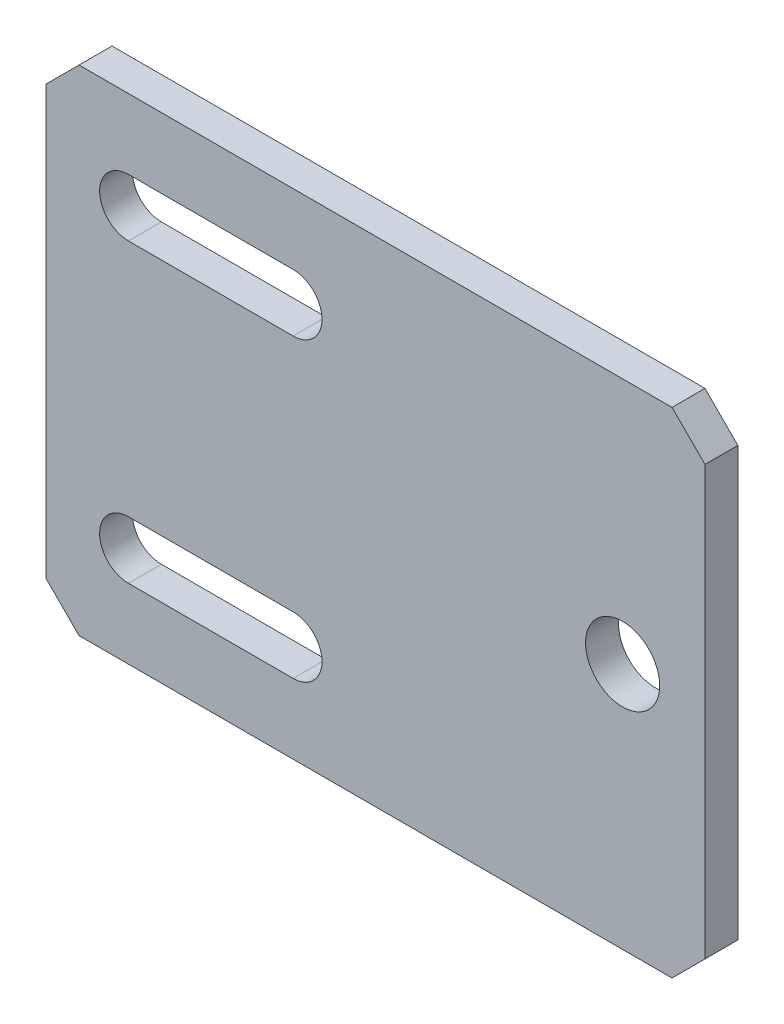
SolidWorks part; units mm, degrees
ref_plane "Front Plane" through (0, 0, 0) normal (0, 0, 1) x (1, 0, 0)
ref_plane "Top Plane" through (0, 0, 0) normal (0, 1, 0) x (1, 0, 0)
ref_plane "Right Plane" through (0, 0, 0) normal (1, 0, 0) x (0, 0, -1)
sketch "Sketch1" plane through (0, 0, 0) normal (0, 0, 1) x (1, 0, 0)
  line L1 (0, 0) -> (40, 0)
  line L2 (0, 0) -> (0, 30)
  line L3 (0, 30) -> (40, 30)
  line L4 (40, 0) -> (40, 30)
  dimension "A" = 40
  dimension "B" = 30
extrude "Boss-Extrude1" add sketch "Sketch1" along normal blind 2
chamfer "Chamfer1" distance 2 angle 45 4 edges at (40, 0, 1) (0, 0, 1) (40, 30, 1) (0, 30, 1)
ref_plane "Dim. X" through (10, 0, 0) normal (1, 0, 0) x (0, 0, -1)
ref_plane "Dim. Y" through (0, 6, 0) normal (0, 1, 0) x (1, 0, 0)
ref_plane "Dim. G_1" through (0, 24, 0) normal (0, 1, 0) x (1, 0, 0)
ref_plane "Dim. S" through (0, 15, 0) normal (0, 1, 0) x (1, 0, 0)
ref_plane "Dim. L" through (35, 0, 0) normal (1, 0, 0) x (0, 0, -1)
sketch "Sketch2" plane through (0, 0, 2) normal (0, 0, 1) x (1, 0, 0)
  line L0 (5, 6) -> (15, 6) construction
  line L1 (5, 7.75) -> (15, 7.75)
  line L2 (5, 4.25) -> (15, 4.25)
  line L3 (10, -0.88) -> (10, 0.88) construction
  line L4 (0.88, 6) -> (-0.88, 6) construction
  circle A0 centre (10, 6) radius 1.5 construction
  circle A1 centre (10, 6) radius 1.75 construction
  arc A2 (5, 7.75) -> (5, 4.25) centre (5, 6) ccw
  arc A3 (15, 4.25) -> (15, 7.75) centre (15, 6) ccw
  point P6 (10, 6)
  dimension "N" = 3
  dimension "D_s_1" = 3.5
  dimension "K" = 10
extrude "N Cut-Extrude1" cut sketch "Sketch2" against normal through all
sketch "Sketch3" plane through (0, 0, 2) normal (0, 0, 1) x (1, 0, 0)
  line L0 (5, 24) -> (15, 24) construction
  line L1 (5, 25.75) -> (15, 25.75)
  line L2 (5, 22.25) -> (15, 22.25)
  line L3 (0.88, 24) -> (-0.88, 24) construction
  line L4 (10, -0.88) -> (10, 0.88) construction
  arc A0 (5, 25.75) -> (5, 22.25) centre (5, 24) ccw
  arc A1 (15, 22.25) -> (15, 25.75) centre (15, 24) ccw
  circle A2 centre (10, 24) radius 1.75 construction
  circle A3 centre (10, 24) radius 1.5 construction
  point P2 (10, 24)
  dimension "D_s_1" = 3.5
  dimension "N" = 3
  dimension "K" = 10
extrude "N Cut-Extrude2" cut sketch "Sketch3" against normal through all
hole_wizard "D Diameter Hole1" positions "Sketch5" profile "Sketch4" hole size "Ø10.0" standard "JIS" end condition through all
sketch "Sketch5" plane through (0, 0, 2) normal (0, 0, 1) x (1, 0, 0)
  line L0 (0.88, 15) -> (-0.88, 15) construction
  line L1 (35, -0.88) -> (35, 0.88) construction
  point P0 (35, 15)
sketch "Sketch4" plane through (35, 15, 2) normal (1, 0, 0) x (0, -1, 0)
  line L0 (0, 0) -> (0, 2)
  line L1 (0, 2) -> (2.25, 2)
  line L2 (2.25, 2) -> (2.25, 0)
  line L5 (2.25, 0) -> (0, 0)
  line L11 (0, 0) -> (0, 2) construction
  dimension "D" = 4.5
  dimension "Thru Hole Depth" = 2
ref_plane "Dim. G_2" [suppressed] through (28, 0, 0) normal (1, 0, 0) x (0, 0, -1)
other "DeleteFace1" [suppressed]
other "DeleteFace2" [suppressed]
sketch "Sketch6" [suppressed] plane through (0, 0, 1.6) normal (0, 0, 1) x (1, 0, 0)
  line L0 (8, 3) -> (8, 7) construction
  line L1 (6.25, 3) -> (6.25, 7)
  line L2 (9.75, 3) -> (9.75, 7)
  line L3 (0.88, 5) -> (-0.88, 5) construction
  line L4 (8, -0.88) -> (8, 0.88) construction
  circle A0 centre (8, 5) radius 1.5 construction
  circle A1 centre (8, 5) radius 1.75 construction
  arc A2 (6.25, 3) -> (9.75, 3) centre (8, 3) ccw
  arc A3 (9.75, 7) -> (6.25, 7) centre (8, 7) ccw
  point P6 (8, 5)
  dimension "N" = 3
  dimension "D_s_1" = 3.5
  dimension "K" = 10
extrude "N Cut-Extrude3" [suppressed] cut sketch "Sketch6" against normal through all
sketch "Sketch7" [suppressed] plane through (0, 0, 1.6) normal (0, 0, 1) x (1, 0, 0)
  line L0 (28, 7) -> (28, 3) construction
  line L1 (29.75, 7) -> (29.75, 3)
  line L2 (26.25, 7) -> (26.25, 3)
  line L3 (0.88, 5) -> (-0.88, 5) construction
  line L4 (28, -0.88) -> (28, 0.88) construction
  arc A0 (29.75, 7) -> (26.25, 7) centre (28, 7) ccw
  arc A1 (26.25, 3) -> (29.75, 3) centre (28, 3) ccw
  circle A2 centre (28, 5) radius 1.75 construction
  circle A3 centre (28, 5) radius 1.5 construction
  point P2 (28, 5)
  dimension "D_s_1" = 3.5
  dimension "N" = 3
  dimension "K" = 10
extrude "N Cut-Extrude4" [suppressed] cut sketch "Sketch7" against normal through all
other "DeleteFace3" [suppressed]
chamfer "Chamfer2" [suppressed] distance 1 angle 45
